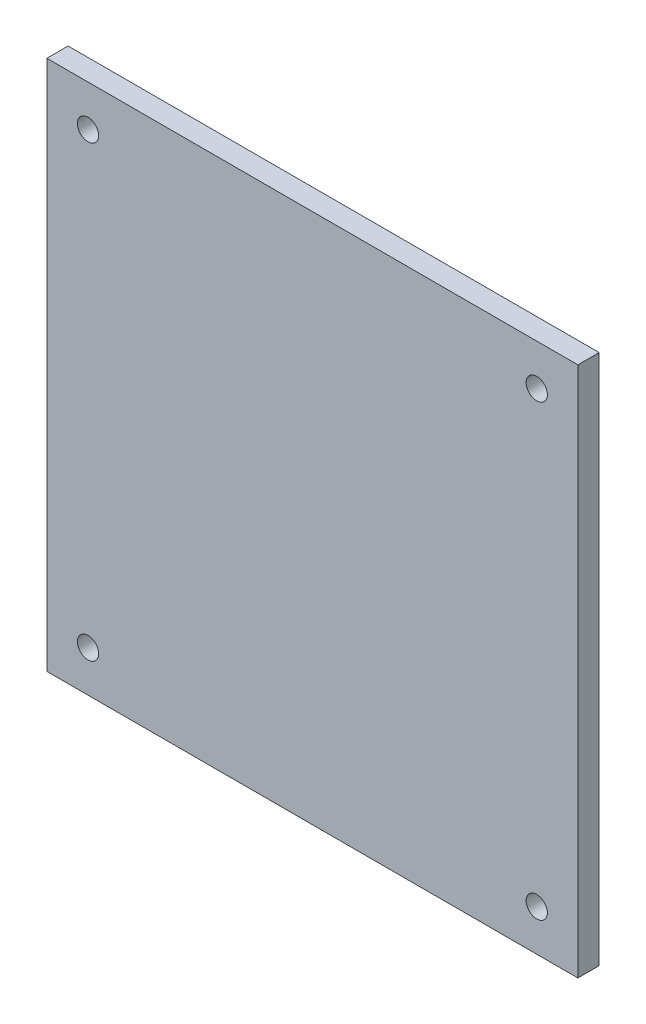
SolidWorks part; units mm, degrees
material "Polyurethane Foam Flexible"
ref_plane "Front" through (0, 0, 0) normal (0, 0, 1) x (1, 0, 0)
ref_plane "Top" through (0, 0, 0) normal (0, 1, 0) x (1, 0, 0)
ref_plane "Right" through (0, 0, 0) normal (1, 0, 0) x (0, 0, -1)
sketch "Sketch2" plane through (0, 0, 0) normal (0, 0, 1) x (1, 0, 0)
  line L1 (105.8661, 1.2283) -> (205.8661, 1.2283)
  line L2 (105.8661, 1.2283) -> (105.8661, 101.2283)
  line L3 (105.8661, 101.2283) -> (205.8661, 101.2283)
  line L4 (205.8661, 1.2283) -> (205.8661, 101.2283)
  circle A0 centre (113.6161, 93.4783) radius 2
  circle A1 centre (198.1161, 93.4783) radius 2
  circle A2 centre (198.1161, 8.9783) radius 2
  circle A3 centre (113.6161, 8.9783) radius 2
  dimension "D3" = 7.75
  dimension "D1" = 100
  dimension "D2" = 100
  dimension "D4" = 7.75
  dimension "D5" = 7.75
base flange "Base-Flange2" sketch "Sketch2" thickness 4 reverse thickness direction no parameters "D1"=1.651
sketch "Bend-Lines3" [suppressed] plane through (0, 0, 0) normal (0, 1, 0) x (1, 0, 0)
sketch "Bounding-Box3" [suppressed] plane through (0, 0, 0) normal (0, 1, 0) x (1, 0, 0)
sheet metal parameters "Sheet-Metal2" thickness 4 parameters "D1"=1.651
flat pattern "Flat-Pattern2" [suppressed]
sketch "Bend-Lines4" plane through (0, 0, 0) normal (0, 1, 0) x (1, 0, 0)
sketch3d "Bounding-Box4" [suppressed]
  line L0 (105.8661, 1.2283, 0) -> (205.8661, 1.2283, 0) construction
  line L1 (105.8661, 101.2283, 0) -> (205.8661, 101.2283, 0) construction
  line L2 (105.8661, 1.2283, 0) -> (105.8661, 101.2283, 0) construction
  line L3 (205.8661, 1.2283, 0) -> (205.8661, 101.2283, 0) construction
